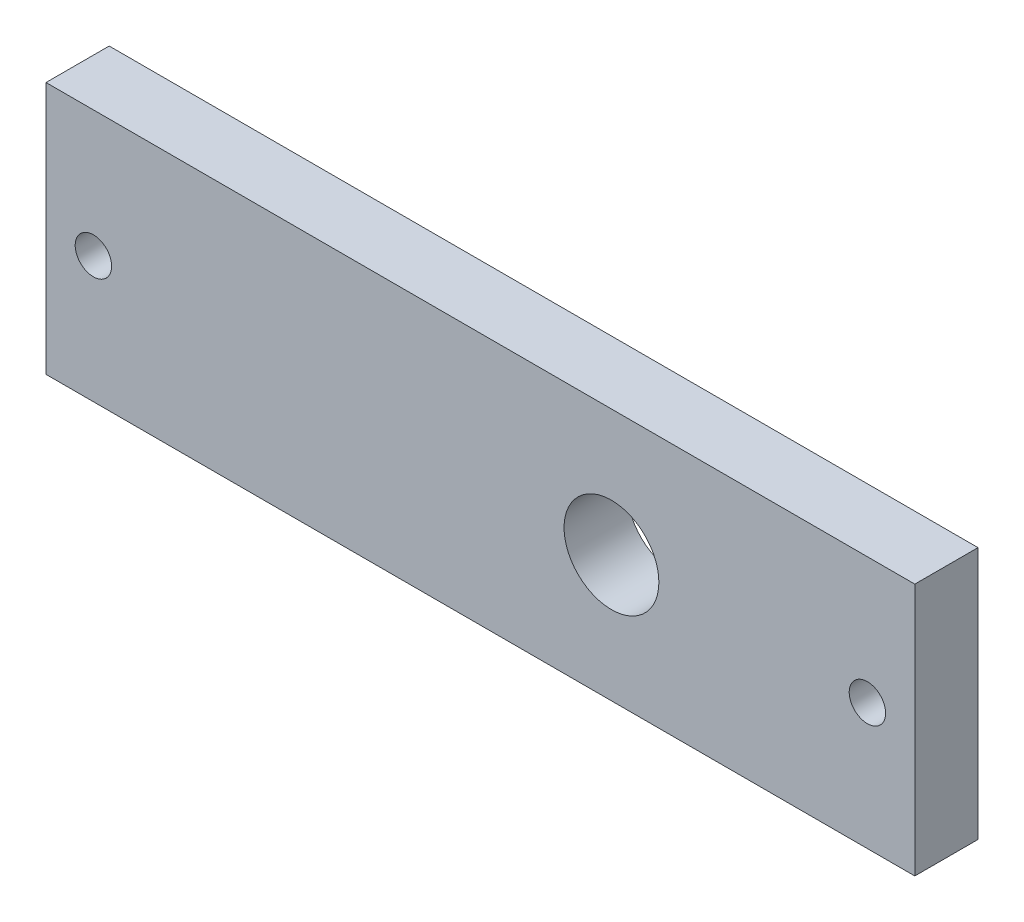
SolidWorks part; units mm, degrees
material "6061-T6 (SS)"
ref_plane "Front" through (0, 0, 0) normal (0, 0, 1) x (1, 0, 0)
ref_plane "Top" through (0, 0, 0) normal (0, 1, 0) x (1, 0, 0)
ref_plane "Right" through (0, 0, 0) normal (1, 0, 0) x (0, 0, -1)
ref_axis "side-side" through (80.9, 0, 0) along (-1, 0, 0)
ref_axis "up-down" through (0, 50, 0) along (0, -1, 0)
ref_axis "front-back" through (0, 0, -80.9) along (0, 0, 1)
sketch "Sketch1" plane through (0, 0, 0) normal (0, 0, 1) x (1, 0, 0)
  line L0 (-38.8875, 12.7) -> (38.8875, 12.7) construction
  line L1 (-43.65, 0) -> (43.65, 0)
  line L2 (-43.65, 0) -> (-43.65, 25.4)
  line L3 (-43.65, 25.4) -> (43.65, 25.4)
  line L4 (43.65, 0) -> (43.65, 25.4)
  circle A0 centre (13.17, 12.7) radius 4.7625
  dimension "D6" = 9.525
  dimension "D7" = 30.48
  dimension "D1" = 25.4
  dimension "D2" = 87.3
  dimension "D3" = 12.7
  dimension "D4" = 4.7625
  dimension "D5" = 4.7625
extrude "Boss-Extrude1" add sketch "Sketch1" along normal mid plane 6.35
hole_wizard "#6 Clearance Hole1" positions "Sketch2" profile "Sketch3" hole size "#6" standard "ANSI Inch" end condition through all
sketch "Sketch2" plane through (0, 0, 3.175) normal (0, 0, 1) x (1, 0, 0)
  point P0 (-38.8875, 12.7)
  point P3 (38.8875, 12.7)
sketch "Sketch3" plane through (-38.8875, 12.7, 3.175) normal (1, 0, 0) x (0, -1, 0)
  line L0 (0, 0) -> (0, 6.35)
  line L1 (0, 6.35) -> (1.8288, 6.35)
  line L2 (1.8288, 6.35) -> (1.8288, 0)
  line L5 (1.8288, 0) -> (0, 0)
  line L11 (0, -6.35) -> (0, 107.95) construction
  dimension "Thru Hole Dia." = 3.6576
  dimension "Thru Hole Depth" = 6.35
